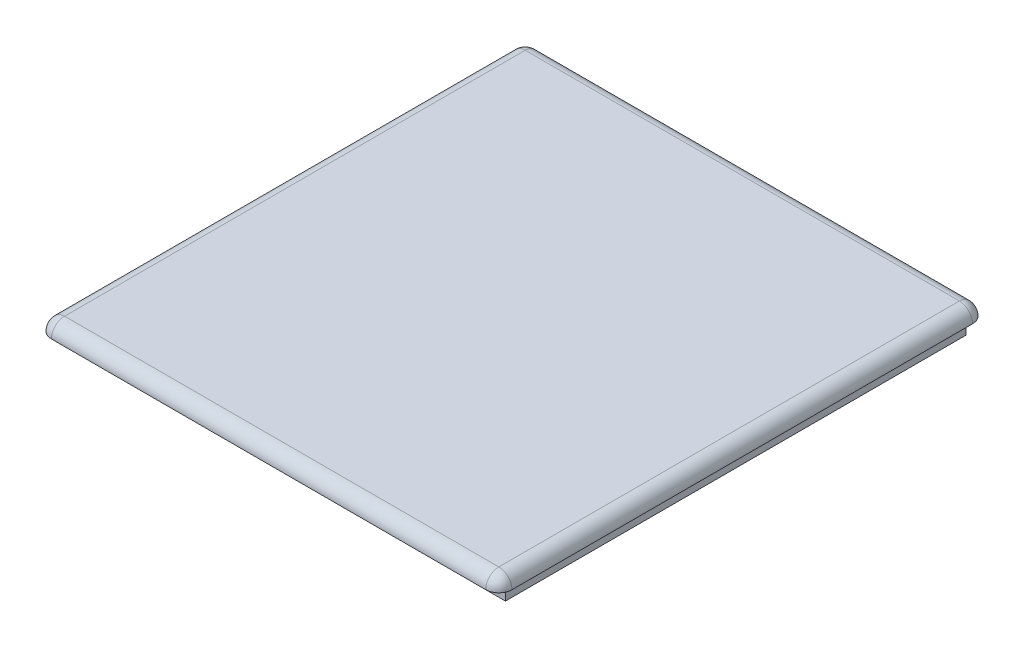
SolidWorks part; units mm, degrees
ref_plane "正面" through (0, 0, 0) normal (0, 0, 1) x (1, 0, 0)
ref_plane "平面" through (0, 0, 0) normal (0, 1, 0) x (1, 0, 0)
ref_plane "右側面" through (0, 0, 0) normal (1, 0, 0) x (0, 0, -1)
sketch "ｽｹｯﾁ1" plane through (0, 0, 0) normal (0, 1, 0) x (1, 0, 0)
  line L0 (-16.6829, 20.2241) -> (17.3171, 20.2241)
  line L1 (-16.6829, 20.2241) -> (-16.6829, -14.7759)
  line L2 (17.3171, 20.2241) -> (17.3171, -14.7759)
  line L3 (-16.6829, -14.7759) -> (17.3171, -14.7759)
  dimension "D1" = 34
  dimension "D2" = 35
extrude "ﾎﾞｽ - 押し出し2" add sketch "ｽｹｯﾁ1" along normal blind 1
sketch "ｽｹｯﾁ3" plane through (0, 1, 0) normal (0, 1, 0) x (1, 0, 0)
  line L0 (-17.1829, 21.2241) -> (17.8171, 21.2241)
  line L1 (-17.1829, 21.2241) -> (-17.1829, -15.7759)
  line L2 (17.8171, 21.2241) -> (17.8171, -15.7759)
  line L3 (-17.1829, -15.7759) -> (17.8171, -15.7759)
  line L7 (-16.6829, 20.2241) -> (-16.6829, -14.7759) construction
  line L8 (17.3171, 20.2241) -> (-16.6829, 20.2241) construction
  point P4 (0.3171, 2.7241)
  point P8 (0.3171, 2.7241)
  dimension "D1" = 17.5
  dimension "D2" = 18.5
  dimension "D3" = 37
  dimension "D4" = 35
  dimension "D5" = 17
  dimension "D6" = 17.5
extrude "ﾎﾞｽ - 押し出し3" add sketch "ｽｹｯﾁ3" along normal blind 1
fillet "ﾌｨﾚｯﾄ1" radius 1 4 edges at (0.3171, 2, 15.7759) (17.8171, 2, -2.7241) (0.3171, 2, -21.2241) (-17.1829, 2, -2.7241)
